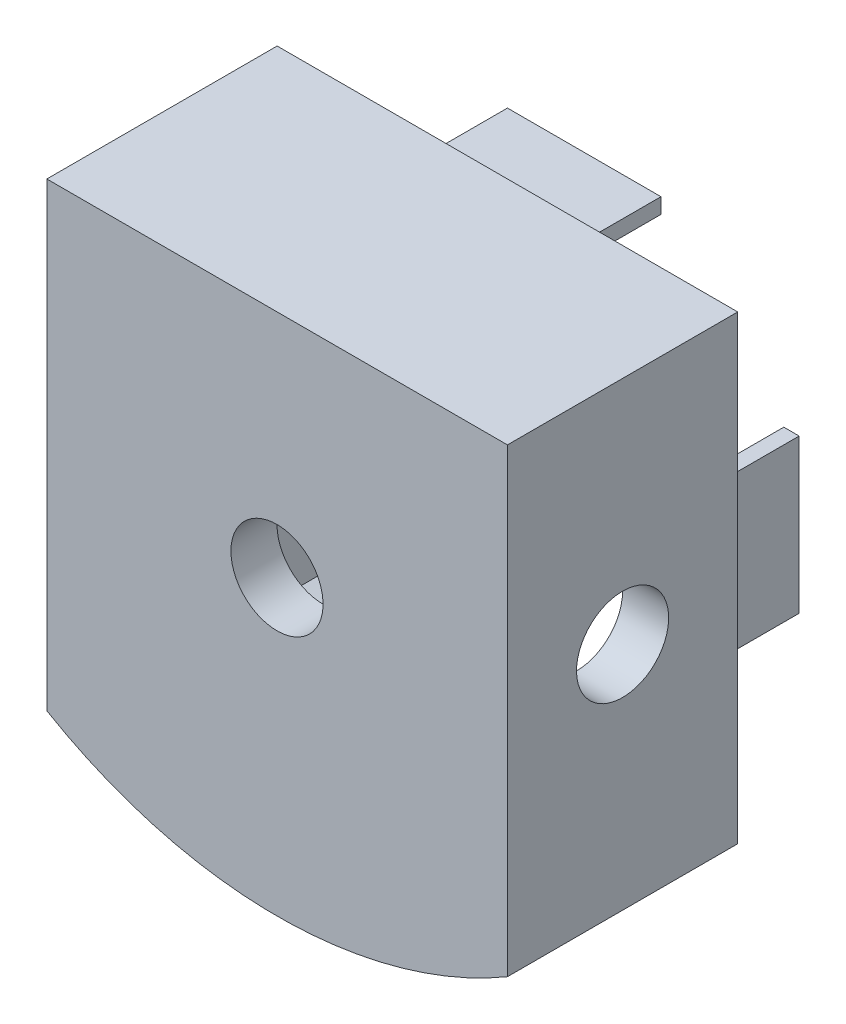
SolidWorks part; units mm, degrees
ref_plane "Front Plane" through (0, 0, 0) normal (0, 0, 1) x (1, 0, 0)
ref_plane "Top Plane" through (0, 0, 0) normal (0, 1, 0) x (1, 0, 0)
ref_plane "Right Plane" through (0, 0, 0) normal (1, 0, 0) x (0, 0, -1)
sketch "Sketch1" plane through (0, 0, 0) normal (0, 0, 1) x (1, 0, 0)
  line L2 (15, -15) -> (15, 15)
  line L3 (15, 15) -> (-15, 15)
  line L4 (-15, -15) -> (-15, 15)
  line L5 (15, -15) -> (-15, 15) construction
  line L6 (15, 15) -> (-15, -15) construction
  arc A3 (-15, -15) -> (15, -15) centre (0, 10.5019) ccw
  point P0 (0, 0)
extrude "Boss-Extrude1" add sketch "Sketch1" along normal blind 15
shell "Shell13" thickness 3 removed face at (0, -1.0211, 0)
sketch "Sketch3" plane through (0, 0, 12) normal (0, 0, -1) x (-1, 0, 0)
  circle A0 centre (0.0103, 0.0076) radius 3
extrude "Cut-Extrude2" cut sketch "Sketch3" against normal blind 3
sketch "Sketch4" plane through (0, 0, 0) normal (0, 0, -1) x (-1, 0, 0)
  line L0 (12, 12) -> (12, -13.2221) construction
  line L1 (-5, 14) -> (5, 14)
  line L2 (-5, 14) -> (-5, 13)
  line L3 (-5, 13) -> (5, 13)
  line L4 (5, 14) -> (5, 13)
  line L5 (-14, 5) -> (-13, 5)
  line L6 (-14, 5) -> (-14, -5)
  line L7 (-14, -5) -> (-13, -5)
  line L8 (-13, 5) -> (-13, -5)
  line L9 (-3.5, -17) -> (3.5, -17)
  line L10 (-3.5, -17) -> (-3.5, -18)
  line L11 (-3.5, -18) -> (3.5, -18)
  line L12 (3.5, -17) -> (3.5, -18)
  line L13 (13, 5) -> (14, 5)
  line L14 (13, 5) -> (13, -5)
  line L15 (13, -5) -> (14, -5)
  line L16 (14, 5) -> (14, -5)
  line L17 (-12, -13.2221) -> (-12, 12) construction
  line L18 (-12, 12) -> (12, 12) construction
  point P16 (0, -17)
  point P18 (-13, 0)
  point P19 (13, 0)
  point P20 (0, 13)
  dimension "D1" = 1
  dimension "D2" = 1
  dimension "D3" = 1
  dimension "D4" = 17
extrude "Boss-Extrude2" add sketch "Sketch4" along normal blind 5
sketch "Sketch5" plane through (15, 0, 0) normal (1, 0, 0) x (0, 0, -1)
  line L0 (-15, 15) -> (-15, -15) construction
  circle A0 centre (-7.5, 0) radius 3
  dimension "D1" = 7.5
extrude "Cut-Extrude3" cut sketch "Sketch5" against normal blind 30
